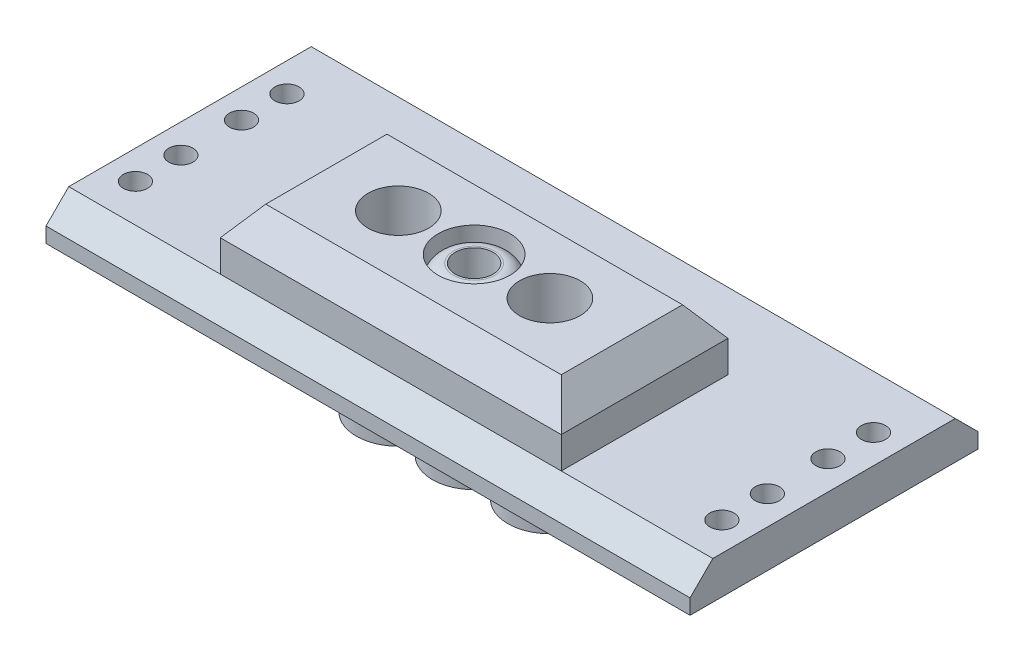
SolidWorks part; units mm, degrees
ref_plane "Alzado" through (0, 0, 0) normal (0, 0, 1) x (1, 0, 0)
ref_plane "Planta" through (0, 0, 0) normal (0, 1, 0) x (1, 0, 0)
ref_plane "Vista lateral" through (0, 0, 0) normal (1, 0, 0) x (0, 0, -1)
sketch "Croquis1" plane through (0, 0, 0) normal (0, 1, 0) x (1, 0, 0)
  line L0 (38.7, -5) -> (38.7, -11) construction
  line L1 (-42.5, -19) -> (42.5, -19)
  line L2 (-42.5, -19) -> (-42.5, 19)
  line L3 (-42.5, 19) -> (42.5, 19)
  line L4 (42.5, -19) -> (42.5, 19)
  line L5 (-42.5, -19) -> (42.5, 19) construction
  line L6 (-42.5, 19) -> (42.5, -19) construction
  line L7 (38.7, -11) -> (-38.7, -11) construction
  line L8 (-38.7, -5) -> (-38.7, -11) construction
  line L9 (38.7, 9) -> (38.7, 3) construction
  line L10 (38.7, 9) -> (38.7, 19) construction
  line L11 (38.7, 9) -> (42.5, 9) construction
  line L12 (-38.7, 9) -> (-38.7, 3) construction
  line L13 (-38.7, 9) -> (-38.7, 19) construction
  line L14 (0, 0) -> (0, -5) construction
  line L15 (-10, -5) -> (10, -5) construction
  circle A0 centre (38.7, -11) radius 1.6
  circle A1 centre (38.7, -5) radius 1.6
  circle A2 centre (-38.7, -11) radius 1.6
  circle A3 centre (-38.7, -5) radius 1.6
  circle A4 centre (38.7, 9) radius 1.6
  circle A5 centre (38.7, 3) radius 1.6
  circle A6 centre (-38.7, 3) radius 1.6
  circle A7 centre (-38.7, 9) radius 1.6
  circle A8 centre (0, -5) radius 2.5
  circle A9 centre (10, -5) radius 2.55
  circle A10 centre (-10, -5) radius 2.55
  point P0 (0, 0)
  point P31 (0, -5)
  point P33 (-16.7, -11)
  dimension "D4" = 3.2
  dimension "D5" = 3.2
  dimension "D6" = 3.2
  dimension "D7" = 3.2
  dimension "D13" = 3.2
  dimension "D14" = 3.2
  dimension "D20" = 3.2
  dimension "D21" = 3.2
  dimension "D22" = 5
  dimension "D24" = 5.1
  dimension "D25" = 5.1
  dimension "D1" = 85
  dimension "D2" = 38
  dimension "D3" = 6
  dimension "D8" = 6
  dimension "D9" = 3.8
  dimension "D10" = 8
  dimension "D11" = 3.8
  dimension "D12" = 6
  dimension "D15" = 3.8
  dimension "D16" = 10
  dimension "D17" = 6
  dimension "D18" = 10
  dimension "D19" = 3.8
  dimension "D23" = 14
  dimension "D26" = 10
extrude "Saliente-Extruir1" add sketch "Croquis1" along normal blind 5
sketch "Croquis2" plane through (0, 5, 0) normal (0, 1, 0) x (1, 0, 0)
  line L0 (-42.5, -19) -> (42.5, -19) construction
  line L1 (0, -5) -> (0, 0) construction
  circle A0 centre (0, -5) radius 4.75
  circle A1 centre (0, -5) radius 2.5
  dimension "D2" = 9.5
  dimension "D3" = 5
  dimension "D1" = 14
extrude "Saliente-Extruir2" add sketch "Croquis2" along normal blind 7
fillet "Redondeo2" radius 2 1 edges at (0, 12, 9.75)
sketch "Croquis4" plane through (0, 5, 0) normal (0, 1, 0) x (1, 0, 0)
  line L0 (0, -5) -> (-10, -5) construction
  line L1 (0, -5) -> (10, -5) construction
  circle A0 centre (10, -5) radius 2.55
  circle A1 centre (-10, -5) radius 2.55
  circle A2 centre (-10, -5) radius 4
  circle A3 centre (10, -5) radius 4
  dimension "D1" = 5.1
  dimension "D2" = 5.1
  dimension "D5" = 8
  dimension "D6" = 8
  dimension "D3" = 10
  dimension "D4" = 10
extrude "Saliente-Extruir3" add sketch "Croquis4" along normal blind 3
fillet "Redondeo3" radius 2 2 edges at (-10, 8, 9) (10, 8, 9)
chamfer "Chaflán1" distance 3 angle 45 2 edges at (0, 5, -19) (0, 5, 19)
sketch "Croquis5" plane through (0, 5, 0) normal (0, 1, 0) x (1, 0, 0)
  line L1 (-22.5, 6) -> (22.5, 6)
  line L2 (-22.5, 6) -> (-22.5, -16)
  line L3 (-22.5, -16) -> (22.5, -16)
  line L4 (22.5, 6) -> (22.5, -16)
  line L5 (-22.5, 6) -> (22.5, -16) construction
  line L6 (-22.5, -16) -> (22.5, 6) construction
  line L7 (-16.5, 2) -> (16.5, 2)
  line L8 (-16.5, 2) -> (-16.5, -12)
  line L9 (-16.5, -12) -> (16.5, -12)
  line L10 (16.5, 2) -> (16.5, -12)
  line L11 (-16.5, 2) -> (16.5, -12) construction
  line L12 (-16.5, -12) -> (16.5, 2) construction
  point P0 (0, -5)
  point P6 (0, -5)
  circle M7 centre (-10, -5) radius 4
  circle M20 centre (0, -5) radius 4.75
  circle M21 centre (10, -5) radius 4
  dimension "D1" = 45
  dimension "D2" = 22
  dimension "D3" = 6
  dimension "D4" = 4
extrude "Saliente-Extruir4" add sketch "Croquis5" along normal blind 8 separate body contours L4 L1 L2 L3 L7 L10 L9 L8 | L8 L9 L7 M20 M7 | L10 L7 L9 M20 M21 region at (0, 5, -5.4991) region at (0, 5, -1.6415)
sketch "Croquis9" plane through (0, 0, 0) normal (0, -1, 0) x (1, 0, 0)
  line L0 (0, -55) -> (0, 55) construction
  circle A0 centre (0, 5) radius 5.5
  circle A1 centre (0, 5) radius 2.5 construction
  circle A2 centre (10, 5) radius 5.55
  circle A3 centre (10, 5) radius 2.55 construction
  circle A4 centre (-10, 5) radius 5.55
  circle M1 centre (10, 5) radius 2.55
  circle M14 centre (0, 5) radius 2.5
  circle M15 centre (-10, 5) radius 2.55
  dimension "D1" = 3
  dimension "D2" = 3
extrude "Saliente-Extruir7" add sketch "Croquis9" along normal blind 10 contours A0 A2 M1 | A0 A4 A2 M14 | A4 A0 M15 | A0 A2 | A4 A0 region at (4.9745, 0, 5) region at (5.5161, 0, 6.2381) region at (4.3017, 0, 5) region at (-4.9745, 0, 5) region at (-5.6533, 0, 5)
chamfer "Chaflán2" distance 3 angle 52 4 edges at (22.5, 13, 5) (-22.5, 13, 5) (0, 13, -6) (0, 13, 16) first distance on face at (0, 13, 5)
